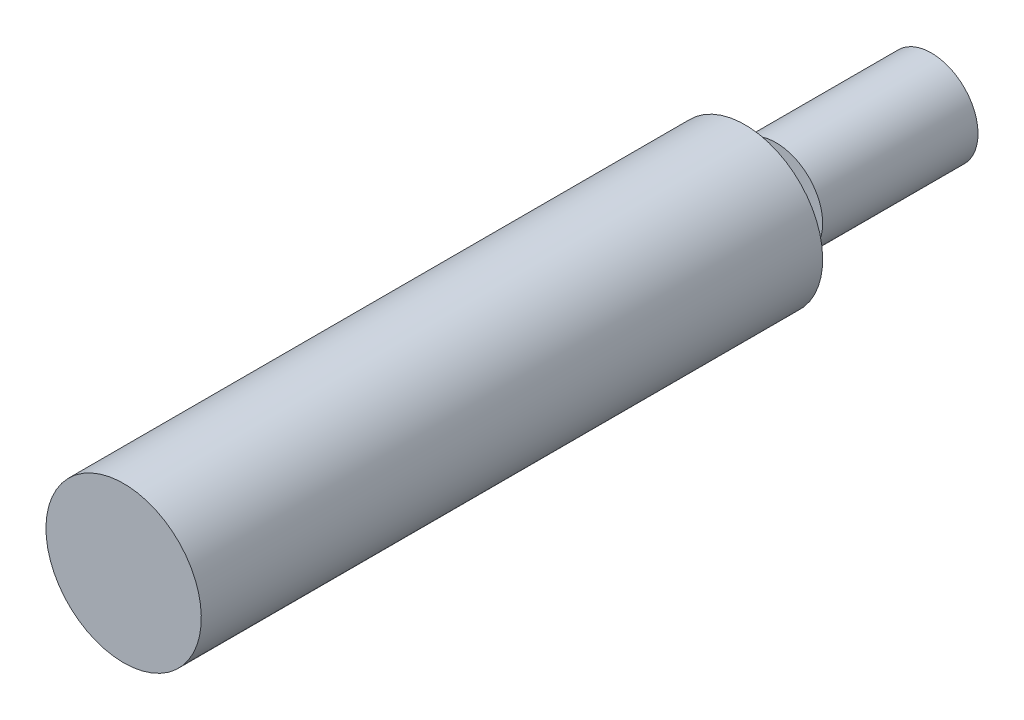
SolidWorks part; units mm, degrees
ref_plane "1" through (0, 0, 0) normal (0, 0, 1) x (1, 0, 0)
ref_plane "2" through (0, 0, 0) normal (0, 1, 0) x (1, 0, 0)
ref_plane "3" through (0, 0, 0) normal (1, 0, 0) x (0, 0, -1)
ref_plane "Front Plane" through (0, 0, 0) normal (0, -1, 0) x (1, 0, 0)
ref_plane "Right Plane" through (0, 0, 0) normal (1, 0, 0) x (0, 1, 0)
ref_plane "Top Plane" through (0, 0, 0) normal (0, 0, 1) x (1, 0, 0)
ref_axis "Axis1" through (0, 0, 50.7014) along (0, 0, -1)
sketch "Sketch1" plane through (0, 0, 0) normal (0, -1, 0) x (1, 0, 0)
  line L0 (0, 44.6812) -> (0, -7.0401) construction
  line L1 (0, 20) -> (2.5, 20)
  line L2 (2.5, 20) -> (2.5, 0)
  line L3 (2.5, 0) -> (1, 0)
  line L4 (0, -6) -> (1.5, -6)
  line L5 (1.5, -6) -> (1.5, -1)
  line L6 (1.5, -1) -> (1, -1)
  line L7 (1, -1) -> (1, 0)
  line L8 (0, -6) -> (0, 20)
  dimension "D1" = 5
  dimension "D2" = 6
  dimension "D3" = 3
  dimension "D4" = 20
  dimension "D5" = 1
  dimension "D6" = 2
revolve "Revolve1" add sketch "Sketch1" angle 360 about L0
